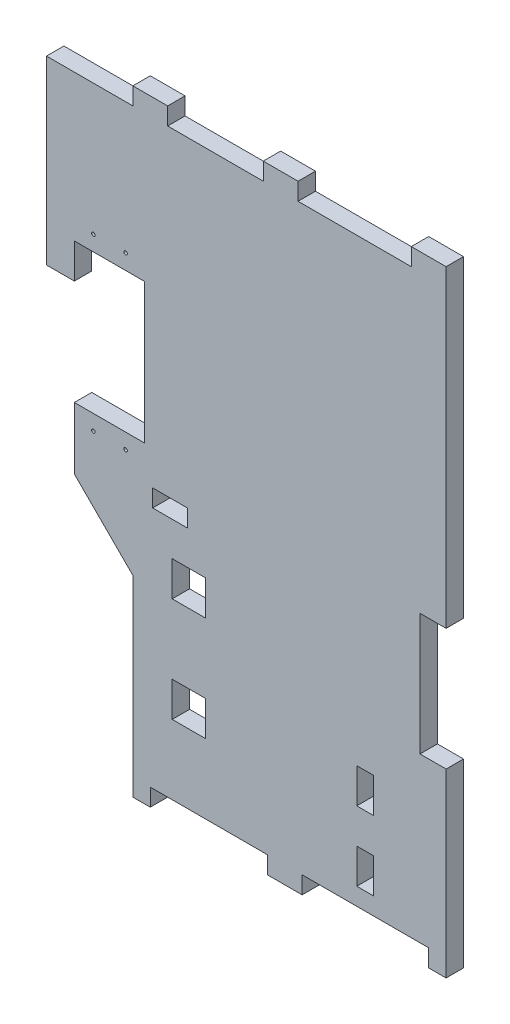
SolidWorks part; units mm, degrees
material "Balsa"
ref_plane "Plan de face" through (0, 0, 0) normal (0, 0, 1) x (1, 0, 0)
ref_plane "Plan de dessus" through (0, 0, 0) normal (0, 1, 0) x (1, 0, 0)
ref_plane "Plan de droite" through (0, 0, 0) normal (1, 0, 0) x (0, 0, -1)
sketch "Esquisse1" plane through (0, 0, 0) normal (0, 0, 1) x (1, 0, 0)
  line L0 (90, 82) -> (90, 167)
  line L1 (5, 0) -> (90, 0)
  line L2 (0, 0) -> (0, 167)
  line L3 (10, 167) -> (80, 167)
  line L4 (90, 0) -> (90, 47)
  line L5 (90, 82) -> (82.5, 82)
  line L6 (0, 167) -> (0, 172)
  line L7 (0, 172) -> (10, 172)
  line L8 (10, 167) -> (10, 172)
  line L9 (0, 0) -> (0, -5)
  line L10 (90, 167) -> (90, 172)
  line L11 (90, 172) -> (80, 172)
  line L12 (80, 167) -> (80, 172)
  line L13 (0, -5) -> (5, -5)
  line L14 (5, 0) -> (5, -5)
  line L15 (64.3348, 35) -> (64.3348, 25)
  line L16 (90, 47) -> (82.5, 47)
  line L17 (82.5, 82) -> (82.5, 47)
  line L18 (64.3348, 35) -> (69.1423, 35)
  line L19 (64.3348, 25) -> (69.1423, 25)
  line L20 (69.1423, 35) -> (69.1423, 25)
  line L21 (71.3405, 35) -> (66.533, 35) construction
  line L22 (64.3348, 35) -> (64.3348, 25) construction
  line L23 (69.1423, 35) -> (69.1423, 25) construction
  line L24 (18.5374, 30) -> (3.1837, 30) construction
  line L25 (64.3348, 15) -> (69.1423, 15)
  line L26 (64.3348, 15) -> (64.3348, 5)
  line L27 (64.3348, 5) -> (69.1423, 5)
  line L28 (69.1423, 15) -> (69.1423, 5)
  line L29 (11.3034, 30) -> (20.8832, 30)
  line L30 (11.3034, 30) -> (11.3034, 20)
  line L31 (11.3034, 20) -> (20.8832, 20)
  line L32 (20.8832, 30) -> (20.8832, 20)
  line L33 (3.1837, 20) -> (18.5374, 20) construction
  line L36 (21.1471, 30) -> (5.7933, 30) construction
  line L37 (11.3034, 60) -> (20.8832, 60)
  line L38 (11.3034, 60) -> (11.3034, 50)
  line L39 (11.3034, 50) -> (20.8832, 50)
  line L40 (20.8832, 60) -> (20.8832, 50)
  dimension "D1" = 167
  dimension "D2" = 90
  dimension "D3" = 10
  dimension "D4" = 5
  dimension "D5" = 5
  dimension "D6" = 7.5
  dimension "D7" = 35
  dimension "D8" = 82
  dimension "D9" = 10
  dimension "D10" = 10
  dimension "D11" = 10
extrude "Boss.-Extru.1" add sketch "Esquisse1" along normal blind 5
sketch "Esquisse2" plane through (0, 0, 5) normal (0, 0, 1) x (1, 0, 0)
  line L0 (0, 172) -> (0, -5) construction
  line L1 (0, 167) -> (-16.8145, 167)
  line L2 (0, 167) -> (0, 50.1855)
  line L3 (0, 50.1855) -> (-16.8145, 67)
  line L4 (-16.8145, 167) -> (-16.8145, 67)
  line L6 (80, 167) -> (10, 167) construction
  dimension "D1" = 16.8145
  dimension "D2" = 135
  dimension "D3" = 100
extrude "Boss.-Extru.2" add sketch "Esquisse2" against normal blind 5
sketch "Esquisse3" plane through (0, 0, 5) normal (0, 0, 1) x (1, 0, 0)
  line L0 (0, 167) -> (-16.8145, 167) construction
  line L1 (3.3855, 125) -> (-16.8145, 125)
  line L2 (3.3855, 125) -> (3.3855, 84.8)
  line L3 (3.3855, 84.8) -> (-16.8145, 84.8)
  line L4 (-16.8145, 125) -> (-16.8145, 84.8)
  line L5 (-16.8145, 167) -> (-16.8145, 67) construction
  dimension "D1" = 42
  dimension "D2" = 20.2
  dimension "D3" = 40.2
extrude "Enlèv. mat.-Extru.1" cut sketch "Esquisse3" against normal blind 5
sketch "Esquisse4" plane through (0, 0, 5) normal (0, 0, 1) x (1, 0, 0)
  line L0 (5, 0) -> (90, 0) construction
  line L1 (-16.8145, 167) -> (-24.8145, 167)
  line L2 (-16.8145, 167) -> (-16.8145, 115)
  line L3 (-16.8145, 115) -> (-24.8145, 115)
  line L4 (-24.8145, 167) -> (-24.8145, 115)
  line L5 (38.6337, 0) -> (48.6337, 0)
  line L6 (38.6337, 0) -> (38.6337, -5)
  line L7 (38.6337, -5) -> (48.6337, -5)
  line L8 (48.6337, 0) -> (48.6337, -5)
  line L9 (92.5017, -5) -> (-34.7153, -5) construction
  line L10 (90, 0) -> (90, 47) construction
  line L11 (90, 0) -> (85, 0)
  line L12 (90, 0) -> (90, -5)
  line L13 (90, -5) -> (85, -5)
  line L14 (85, 0) -> (85, -5)
  line L15 (80, 167) -> (10, 167) construction
  line L16 (0, 50.1855) -> (0, -5) construction
  line L17 (37.4664, 167) -> (47.4664, 167)
  line L18 (37.4664, 167) -> (37.4664, 172)
  line L19 (37.4664, 172) -> (47.4664, 172)
  line L20 (47.4664, 167) -> (47.4664, 172)
  dimension "D1" = 8
  dimension "D2" = 52
  dimension "D3" = 5
  dimension "D4" = 5
  dimension "D5" = 10
  dimension "D6" = 38.6337
  dimension "D7" = 5
  dimension "D8" = 10
extrude "Boss.-Extru.3" add sketch "Esquisse4" against normal blind 5
sketch "Esquisse5" plane through (0, 0, 5) normal (0, 0, 1) x (1, 0, 0)
  circle A0 centre (-11.3395, 129.4) radius 0.5
  circle A1 centre (-2.0895, 129.4) radius 0.5
  circle A2 centre (-11.3395, 80.4) radius 0.5
  circle A3 centre (-2.0895, 80.4) radius 0.5
  dimension "D1" = 1
extrude "Enlèv. mat.-Extru.2" cut sketch "Esquisse5" against normal blind 5
sketch "Esquisse6" plane through (0, 0, 5) normal (0, 0, 1) x (1, 0, 0)
  line L0 (5.6858, 74.8) -> (15.6858, 74.8)
  line L1 (5.6858, 74.8) -> (5.6858, 69.8023)
  line L2 (15.6858, 74.8) -> (15.6858, 69.8023)
  line L3 (5.6858, 69.8023) -> (15.6858, 69.8023)
extrude "Enlèv. mat.-Extru.3" cut sketch "Esquisse6" against normal blind 10
